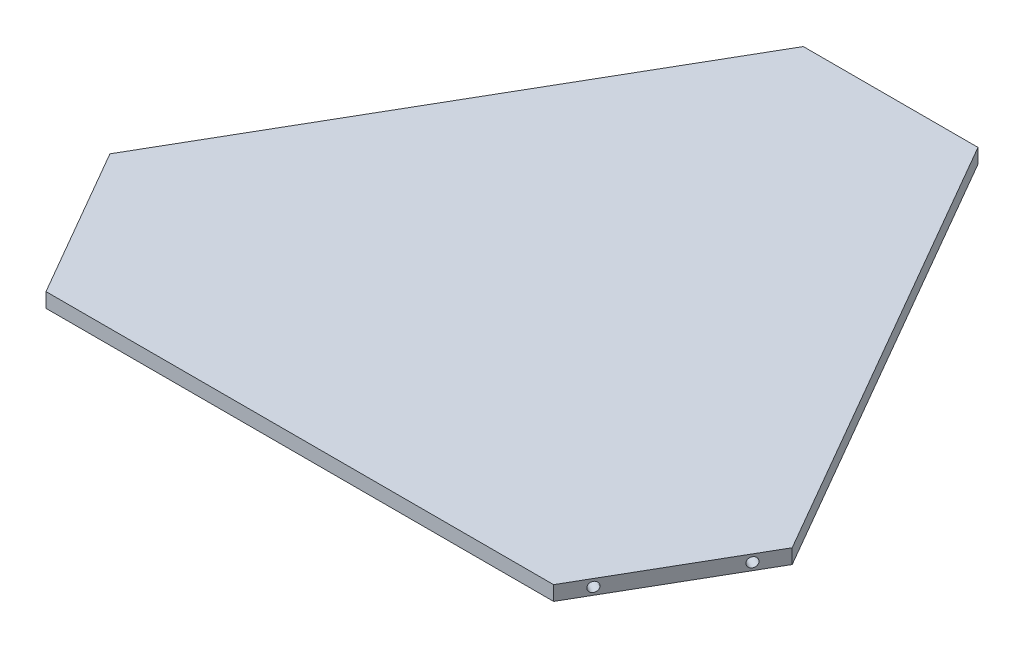
SolidWorks part; units mm, degrees
material "Acrylic (Medium-high impact)"
ref_plane "Front Plane" through (0, 0, 0) normal (0, 0, 1) x (1, 0, 0)
ref_plane "Top Plane" through (0, 0, 0) normal (0, 1, 0) x (1, 0, 0)
ref_plane "Right Plane" through (0, 0, 0) normal (1, 0, 0) x (0, 0, -1)
sketch "Sketch1" plane through (0, 0, 0) normal (0, 1, 0) x (1, 0, 0)
  line L0 (-148.8326, -41.9344) -> (-110.7326, -107.9256)
  line L1 (0, 215.8511) -> (-186.9326, -107.9256) construction
  line L2 (-186.9326, -107.9256) -> (186.9326, -107.9256) construction
  line L3 (186.9326, -107.9256) -> (0, 215.8511) construction
  line L4 (-110.7326, -107.9256) -> (110.7326, -107.9256)
  line L5 (110.7326, -107.9256) -> (148.8326, -41.9344)
  line L6 (148.8326, -41.9344) -> (38.1, 149.86)
  line L7 (38.1, 149.86) -> (-38.1, 149.86)
  line L8 (-38.1, 149.86) -> (-148.8326, -41.9344)
  circle A0 centre (0, 0) radius 107.9256 construction
  dimension "D1" = 120
  dimension "D2" = 120
  dimension "D3" = 149.86
  dimension "D4" = 76.2
extrude "Boss-Extrude1" add sketch "Sketch1" along normal blind 6.35
hole_wizard "M5x0.8 Tapped Hole1" positions "Sketch2" profile "Sketch3" tap size "M5x0.8" standard "ANSI Metric"
sketch "Sketch2" plane through (129.7826, 0, 74.93) normal (0.866, 0, 0.5) x (0.5, 0, -0.866)
  line L0 (-25.4, 3.175) -> (25.4, 3.175) construction
  line L3 (38.1, 6.35) -> (38.1, 0) construction
  point P0 (-25.4, 3.175)
  point P2 (25.4, 3.175)
  point P10 (0, 3.175)
  point P15 (38.1, 3.175)
  dimension "D1" = 50.8
cosmetic thread "Hole Thread1" parameters "D1"=2.286, "D2"=5
cosmetic thread "Hole Thread2" parameters "D1"=2.286, "D2"=5
sketch "Sketch3" plane through (117.0826, 3.175, 96.927) normal (0, 1, 0) x (0.5, 0, -0.866)
  line L0 (0, 0) -> (0, 13.9618)
  line L1 (0, 13.9618) -> (2.1, 12.7)
  line L2 (2.1, 12.7) -> (2.1, 0)
  line L5 (2.1, 0) -> (0, 0)
  line L10 (0, 13.9618) -> (-2.1, 12.7) construction
  line L11 (0, -6.35) -> (0, 107.95) construction
  dimension "Tap Drill Dia." = 4.2
  dimension "Tap Drill Depth" = 12.7
  dimension "Drill Angle" = 118
ref_axis "Axis1" through (0, 6.6675, 0) along (0, -1, 0)
pattern_circular "CirPattern1" count 3 over 360 about axis through (0, 6.6675, 0) along (0, -1, 0) of "M5x0.8 Tapped Hole1"
